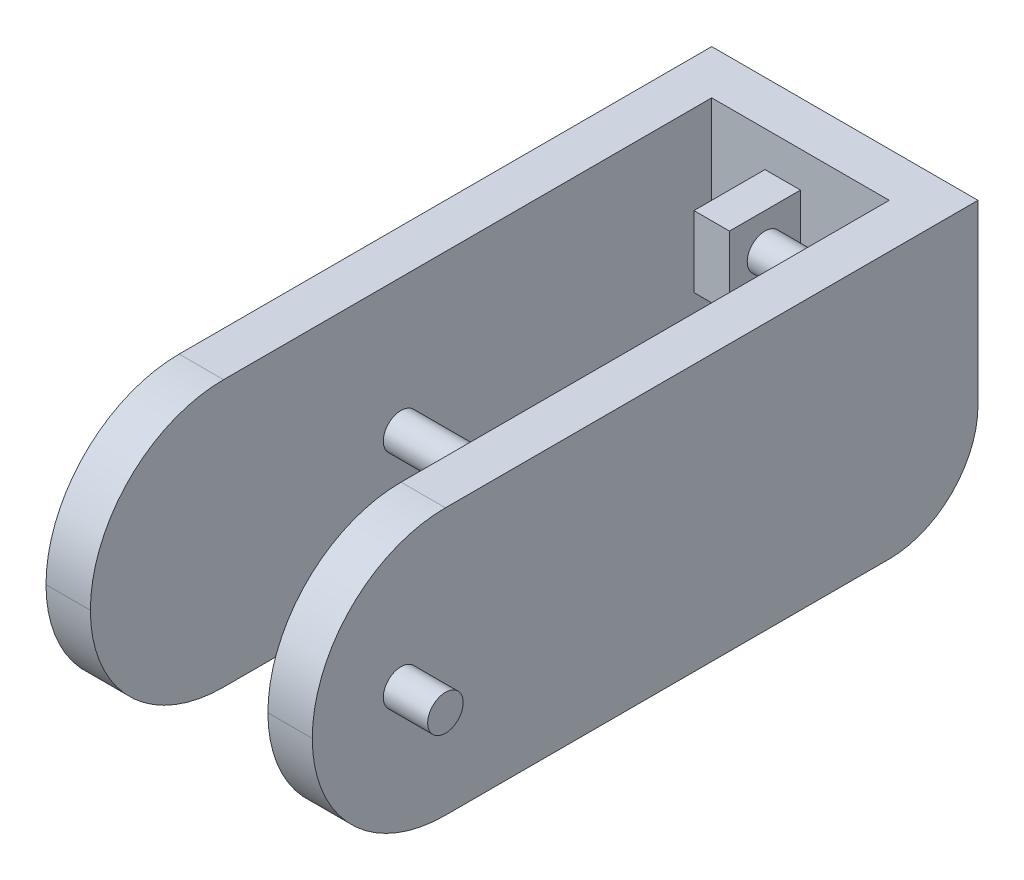
SolidWorks part; units mm, degrees
ref_plane "Front Plane" through (0, 0, 0) normal (0, 0, 1) x (1, 0, 0)
ref_plane "Top Plane" through (0, 0, 0) normal (0, 1, 0) x (1, 0, 0)
ref_plane "Right Plane" through (0, 0, 0) normal (1, 0, 0) x (0, 0, -1)
sketch "Sketch1" plane through (0, 0, 0) normal (0, 1, 0) x (1, 0, 0)
  line L0 (-7.5, -17.5) -> (-7.5, 20)
  line L2 (-5, -17.5) -> (-5, 17.5)
  line L3 (-5, 17.5) -> (5, 17.5)
  line L4 (5, -17.5) -> (5, 17.5)
  line L5 (-5, -17.5) -> (5, 17.5) construction
  line L6 (-5, 17.5) -> (5, -17.5) construction
  line L7 (-7.5, 20) -> (7.5, 20)
  line L8 (7.5, -17.5) -> (7.5, 20)
  line L10 (-5, -17.5) -> (-7.5, -17.5)
  line L11 (5, -17.5) -> (7.5, -17.5)
  line L12 (7.5, -20) -> (7.5, 20) construction
  line L13 (-7.5, -20) -> (7.5, -20) construction
  line L14 (-7.5, -20) -> (-7.5, 20) construction
  line L15 (-5, -17.5) -> (5, -17.5) construction
  point P0 (0, 0)
  dimension "D1" = 10
  dimension "D2" = 35
  dimension "D3" = 2.5
extrude "Boss-Extrude1" add sketch "Sketch1" along normal blind 15
sketch "Sketch4" plane through (5, 0, 0) normal (-1, 0, 0) x (0, 0, 1)
  line L0 (-20, 0) -> (17.5, 0) construction
  line L1 (-20, 15) -> (-20, 0) construction
  circle A0 centre (0, 7.5) radius 1
  dimension "D1" = 2
  dimension "D3" = 20
  dimension "D2" = 7.5
extrude "Boss-Extrude3" add sketch "Sketch4" along normal blind 10
sketch "Sketch5" plane through (7.5, 0, 0) normal (1, 0, 0) x (0, 0, -1)
  line L0 (-17.5, 0) -> (20, 0) construction
  line L1 (-17.5, 15) -> (-17.5, 0) construction
  circle A0 centre (-12.5, 7.5) radius 1
  dimension "D1" = 2
  dimension "D2" = 7.5
  dimension "D3" = 5
extrude "Boss-Extrude4" add sketch "Sketch5" along normal blind 2.5
sketch "Sketch6" plane through (0, 0, -20) normal (0, 0, -1) x (-1, 0, 0)
  line L0 (-7.5, 0) -> (7.5, 0) construction
  line L1 (5, 5) -> (-5, 5)
  line L2 (5, 5) -> (5, 0)
  line L3 (5, 0) -> (-5, 0)
  line L4 (-5, 5) -> (-5, 0)
  line L5 (5, 5) -> (-5, 0) construction
  line L6 (5, 0) -> (-5, 5) construction
  point P0 (0, 2.5)
  point P15 (0, 0)
  dimension "D1" = 10
  dimension "D2" = 5
extrude "Cut-Extrude1" cut sketch "Sketch6" against normal up to next
fillet "Fillet1" radius 7.5 4 edges at (-6.25, 0, 17.5) (-6.25, 15, 17.5) (6.25, 0, 17.5) (6.25, 15, 17.5)
fillet "Fillet2" radius 5 2 edges at (6.25, 0, -20) (-6.25, 0, -20)
sketch "Sketch7" plane through (0, 0, -17.5) normal (0, 0, 1) x (1, 0, 0)
  line L0 (0, -8.25) -> (0, 8.25) construction
  line L1 (0, 9) -> (-2, 9)
  line L3 (0, 13) -> (-2, 13)
  line L4 (-2, 9) -> (-2, 13)
  line L5 (-5, 15) -> (5, 15) construction
  line L8 (0, 9) -> (0, 13)
  point P0 (0, 11)
  point P2 (-1.8352, 13.7181)
  point P3 (0, 0)
  point P11 (0.4016, 13.6872)
  dimension "D1" = 4
  dimension "D2" = 4
  dimension "D3" = 2
extrude "Boss-Extrude5" add sketch "Sketch7" along normal blind 4
sketch "Sketch8" plane through (0, 0, 0) normal (1, 0, 0) x (0, 0, -1)
  line L0 (13.5, 13) -> (17.5, 13) construction
  line L1 (13.5, 9) -> (13.5, 13) construction
  circle A0 centre (15.5, 11) radius 1
  dimension "D1" = 2
  dimension "D2" = 2
  dimension "D3" = 2
extrude "Boss-Extrude6" add sketch "Sketch8" along normal blind 2
